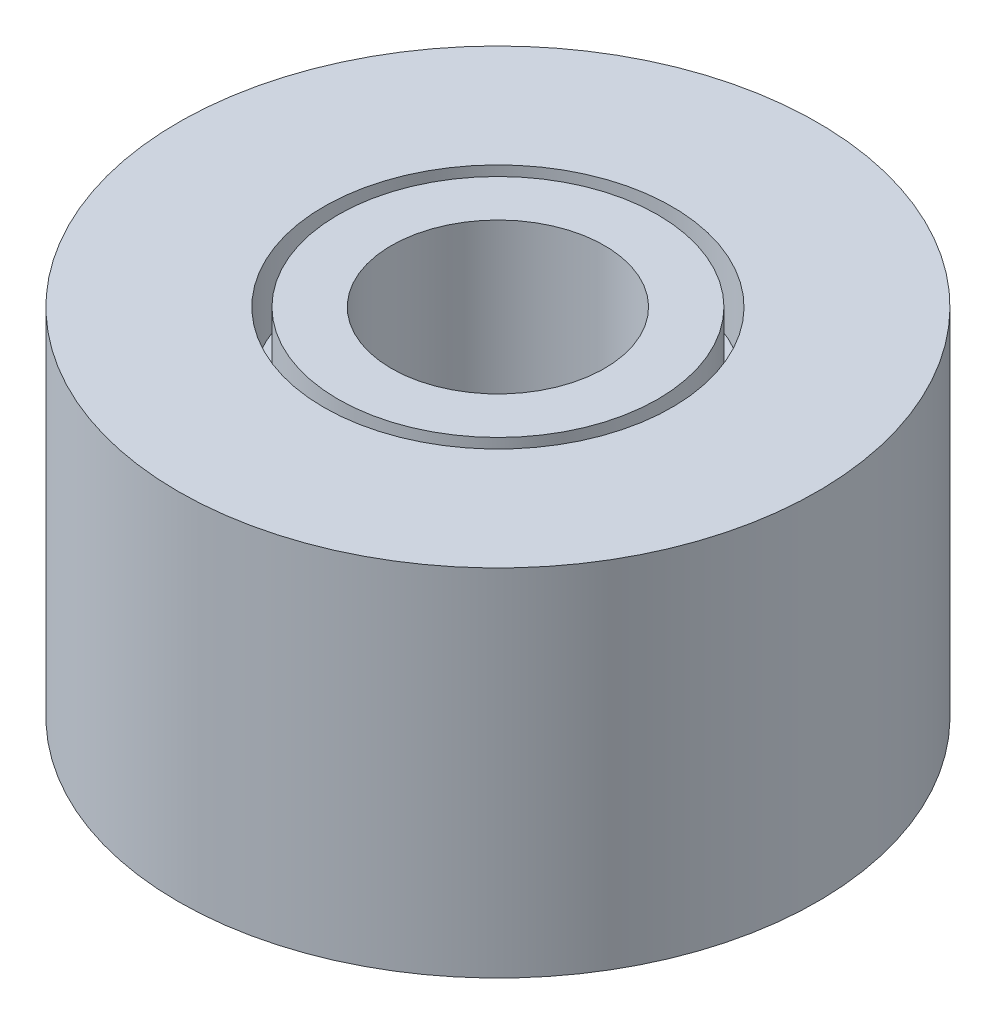
SolidWorks part; units mm, degrees
ref_plane "前视基准面" through (0, 0, 0) normal (0, 0, 1) x (1, 0, 0)
ref_plane "上视基准面" through (0, 0, 0) normal (0, 1, 0) x (1, 0, 0)
ref_plane "右视基准面" through (0, 0, 0) normal (1, 0, 0) x (0, 0, -1)
other "Configuration Table"
sketch "草图1" plane through (0, 0, 0) normal (0, 1, 0) x (1, 0, 0)
  circle A0 centre (0, 0) radius 4.5
  circle A1 centre (0, 0) radius 1.5
  circle A2 centre (0, 0) radius 2.25
  dimension "D1" = 3
  dimension "D2" = 9
  dimension "D3" = 4.5
extrude "凸台-拉伸1" add sketch "草图1" along normal blind 5 contours A1 | A0 region at (0, 0, 0)
extrude "切除-拉伸-薄壁1" cut sketch "草图1<3>" along normal blind 1 thin contours A2 thin type one direction wall 0.2
sketch "草图1<3>" plane through (0, 0, 0) normal (0, 1, 0) x (1, 0, 0) same geometry as "草图1"
extrude "切除-拉伸-薄壁2" cut sketch "草图1<4>" against normal blind 1 from surface thin contours A2 starting at face at (0, 5, 4.5) thin type one direction wall 0.2
sketch "草图1<4>" plane through (0, 0, 0) normal (0, 1, 0) x (1, 0, 0) same geometry as "草图1"
